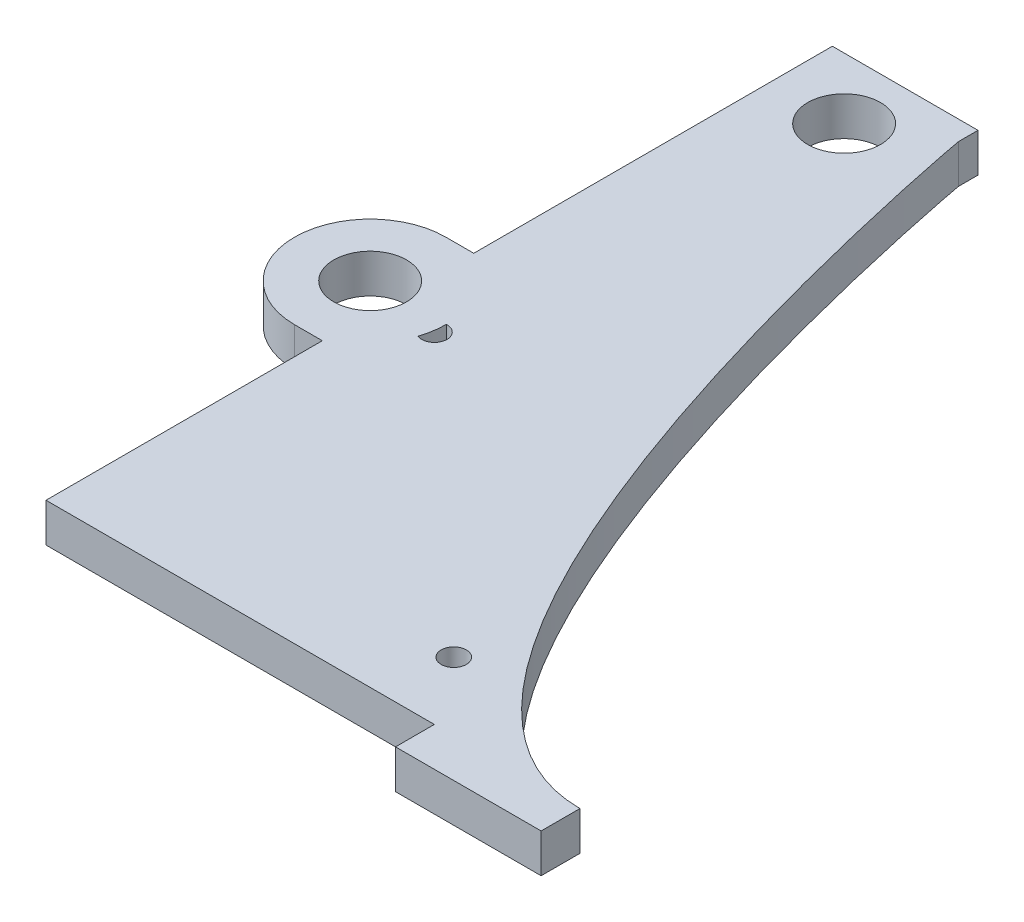
SolidWorks part; units mm, degrees
ref_plane "Front Plane" through (0, 0, 0) normal (0, 0, 1) x (1, 0, 0)
ref_plane "Top Plane" through (0, 0, 0) normal (0, 1, 0) x (1, 0, 0)
ref_plane "Right Plane" through (0, 0, 0) normal (1, 0, 0) x (0, 0, -1)
sketch "Sketch1" plane through (0, 0, 0) normal (0, 1, 0) x (1, 0, 0)
  line L0 (9.525, -53.975) -> (60.325, -53.975) construction
  line L1 (-9.525, -53.975) -> (9.525, -53.975) construction
  line L2 (-9.525, -53.975) -> (-9.525, 53.975) construction
  line L3 (-9.525, 53.975) -> (9.525, 53.975)
  line L4 (9.525, -53.975) -> (9.525, 53.975) construction
  line L5 (-9.525, -53.975) -> (9.525, 53.975) construction
  line L6 (-9.525, 53.975) -> (9.525, -53.975) construction
  line L7 (0, 53.975) -> (0, 45.9867) construction
  line L8 (-9.525, 50.7492) -> (9.525, 50.7492) construction
  line L9 (9.525, 51.435) -> (9.525, 53.975)
  line L10 (60.325, -53.975) -> (60.325, -48.895) construction
  line L11 (60.325, -48.895) -> (-9.525, -48.895) construction
  line L12 (60.325, -53.975) -> (60.325, -48.895) construction
  line L13 (60.325, -48.895) -> (-9.525, -48.895)
  line L14 (-9.525, -48.895) -> (-9.525, 53.975)
  line L15 (31.115, -19.685) -> (31.115, -48.895) construction
  circle A0 centre (0, 45.9867) radius 4.7625
  spline S0 degree 3 poles (9.525, 51.435) (9.525, 51.2145) (27.8191, -48.895) (60.325, -48.895) knots 0 0 0 0 1 1 1 1
  point P4 (0, 0)
  dimension "D5" = 9.525
  dimension "D1" = 107.95
  dimension "D2" = 19.05
  dimension "D3" = 50.8
  dimension "D4" = 2.54
  dimension "D6" = 104.7242
  dimension "D7" = 5.08
  dimension "D8" = 40.64
  dimension "D9" = 29.21
extrude "Boss-Extrude1" add sketch "Sketch1" along normal blind 5.08
sketch "Sketch4" plane through (0, 5.08, 0) normal (0, 1, 0) x (1, 0, 0)
  line L0 (-9.525, 53.975) -> (-9.525, -48.895) construction
  line L1 (60.325, -48.895) -> (41.275, -48.895)
  line L2 (60.325, -48.895) -> (60.325, -53.975)
  line L3 (60.325, -53.975) -> (41.275, -53.975)
  line L4 (41.275, -48.895) -> (41.275, -53.975)
  line L5 (60.325, -48.895) -> (41.275, -53.975) construction
  line L6 (60.325, -53.975) -> (41.275, -48.895) construction
  point P4 (50.8, -51.435)
  dimension "D1" = 50.8
  dimension "D2" = 5.08
extrude "Boss-Extrude2" add sketch "Sketch4" against normal up to surface (5.08 mm away) up to face at (17.145, 0, -2.286)
sketch "Sketch5" plane through (0, 0, 0) normal (0, -1, 0) x (1, 0, 0)
  circle A1 centre (34.925, 40.005) radius 1.651
  circle A3 centre (-3.175, 4.445) radius 1.6607
extrude "Cut-Extrude1" cut sketch "Sketch5" against normal through all both
sketch "Sketch6" plane through (0, 0, 0) normal (0, -1, 0) x (1, 0, 0)
  line L0 (-9.525, 2.8423) -> (-13.1707, 2.8423) construction
  line L1 (-9.525, -53.975) -> (-9.525, 48.895) construction
  line L2 (-13.1707, 12.7483) -> (-9.525, 12.7483)
  line L3 (-13.1707, -7.0637) -> (-9.525, -7.0637)
  line L4 (-9.525, 12.7483) -> (-9.525, 12.053)
  line L5 (-9.525, -7.0637) -> (-9.525, -6.3685)
  line L6 (41.275, 53.975) -> (60.325, 53.975) construction
  circle A0 centre (-13.1707, 2.8423) radius 4.7625
  arc A1 (-9.525, -6.3685) -> (-9.525, 12.053) centre (-13.1707, 2.8423) ccw
  arc A2 (-13.1707, 12.7483) -> (-13.1707, -7.0637) centre (-13.1707, 2.8423) ccw
  dimension "D1" = 9.525
  dimension "D3" = 19.812
  dimension "D2" = 3.6457
  dimension "D4" = 51.1327
extrude "Boss-Extrude3" add sketch "Sketch6" against normal blind 5.08
sketch "Sketch8" plane through (0, 5.08, 0) normal (0, 1, 0) x (1, 0, 0)
  circle A0 centre (-13.1707, -2.8423) radius 4.7625
extrude "Cut-Extrude2" cut sketch "Sketch8" against normal through all
